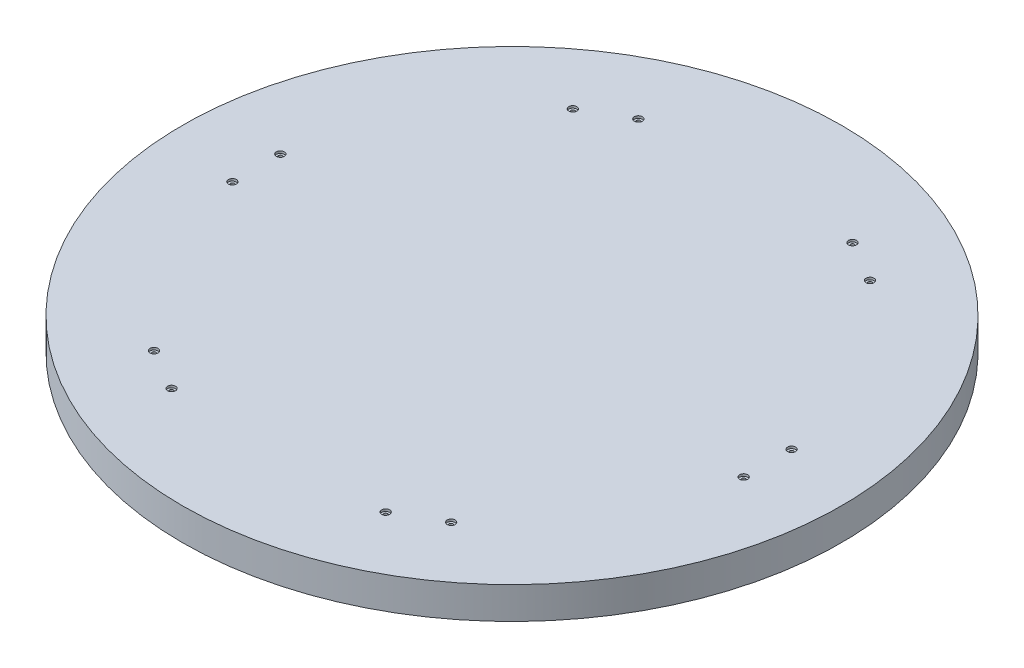
SolidWorks part; units mm, degrees
ref_plane "Front Plane" through (0, 0, 0) normal (0, 0, 1) x (1, 0, 0)
ref_plane "Top Plane" through (0, 0, 0) normal (0, 1, 0) x (1, 0, 0)
ref_plane "Right Plane" through (0, 0, 0) normal (1, 0, 0) x (0, 0, -1)
sketch "Sketch1" plane through (0, 0, 0) normal (0, 1, 0) x (1, 0, 0)
  circle A0 centre (0, 0) radius 261.9375
extrude "Boss-Extrude1" add sketch "Sketch1" along normal blind 25.4
sketch "Sketch6" plane through (0, 0, 0) normal (0, -1, 0) x (1, 0, 0)
  line L0 (203.2, 19.05) -> (203.2, -19.05) construction
  line L1 (215.9, 19.05) -> (215.9, -19.05)
  line L2 (190.5, 19.05) -> (190.5, -19.05)
  line L3 (203.2, -16.5451) -> (201.0307, -17.7976) construction
  line L4 (201.0307, -17.7976) -> (201.0307, -20.3024) construction
  line L5 (201.0307, -20.3024) -> (203.2, -21.5549) construction
  line L6 (203.2, -21.5549) -> (205.3693, -20.3024) construction
  line L7 (205.3693, -20.3024) -> (205.3693, -17.7976) construction
  line L8 (205.3693, -17.7976) -> (203.2, -16.5451) construction
  line L9 (203.2, 22.1294) -> (201.0307, 20.8769) construction
  line L10 (201.0307, 20.8769) -> (201.0307, 18.372) construction
  line L11 (201.0307, 18.372) -> (203.2, 17.1196) construction
  line L12 (203.2, 17.1196) -> (205.3693, 18.372) construction
  line L13 (205.3693, 18.372) -> (205.3693, 20.8769) construction
  line L14 (205.3693, 20.8769) -> (203.2, 22.1294) construction
  line L15 (0, 0) -> (203.2, 0) construction
  line L16 (87.2715, -184.2489) -> (85.1022, -182.9965) construction
  line L17 (85.1022, -182.9965) -> (82.9329, -184.2489) construction
  line L18 (82.9329, -184.2489) -> (82.9329, -186.7538) construction
  line L19 (82.9329, -186.7538) -> (85.1022, -188.0063) construction
  line L20 (85.1022, -188.0063) -> (87.2715, -186.7538) construction
  line L21 (87.2715, -186.7538) -> (87.2715, -184.2489) construction
  line L22 (120.7646, -164.9117) -> (118.5953, -163.6592) construction
  line L23 (118.5953, -163.6592) -> (116.426, -164.9117) construction
  line L24 (116.426, -164.9117) -> (116.426, -167.4166) construction
  line L25 (116.426, -167.4166) -> (118.5953, -168.669) construction
  line L26 (118.5953, -168.669) -> (120.7646, -167.4166) construction
  line L27 (120.7646, -167.4166) -> (120.7646, -164.9117) construction
  line L28 (0, 0) -> (101.6, -175.9764) construction
  line L29 (118.0978, -166.4514) -> (85.1022, -185.5014) construction
  line L30 (124.4478, -177.4499) -> (91.4522, -196.4999)
  line L31 (111.7478, -155.4528) -> (78.7522, -174.5028)
  line L32 (-115.9285, -167.7038) -> (-115.9285, -165.1989) construction
  line L33 (-115.9285, -165.1989) -> (-118.0978, -163.9465) construction
  line L34 (-118.0978, -163.9465) -> (-120.2671, -165.1989) construction
  line L35 (-120.2671, -165.1989) -> (-120.2671, -167.7038) construction
  line L36 (-120.2671, -167.7038) -> (-118.0978, -168.9563) construction
  line L37 (-118.0978, -168.9563) -> (-115.9285, -167.7038) construction
  line L38 (-82.4354, -187.0411) -> (-82.4354, -184.5362) construction
  line L39 (-82.4354, -184.5362) -> (-84.6047, -183.2837) construction
  line L40 (-84.6047, -183.2837) -> (-86.774, -184.5362) construction
  line L41 (-86.774, -184.5362) -> (-86.774, -187.0411) construction
  line L42 (-86.774, -187.0411) -> (-84.6047, -188.2935) construction
  line L43 (-84.6047, -188.2935) -> (-82.4354, -187.0411) construction
  line L44 (0, 0) -> (-101.6, -175.9764) construction
  line L45 (-85.1022, -185.5014) -> (-118.0978, -166.4514) construction
  line L46 (-91.4522, -196.4999) -> (-124.4478, -177.4499)
  line L47 (-78.7522, -174.5028) -> (-111.7478, -155.4528)
  line L48 (-203.2, 16.5451) -> (-201.0307, 17.7976) construction
  line L49 (-201.0307, 17.7976) -> (-201.0307, 20.3024) construction
  line L50 (-201.0307, 20.3024) -> (-203.2, 21.5549) construction
  line L51 (-203.2, 21.5549) -> (-205.3693, 20.3024) construction
  line L52 (-205.3693, 20.3024) -> (-205.3693, 17.7976) construction
  line L53 (-205.3693, 17.7976) -> (-203.2, 16.5451) construction
  line L54 (-203.2, -22.1294) -> (-201.0307, -20.8769) construction
  line L55 (-201.0307, -20.8769) -> (-201.0307, -18.372) construction
  line L56 (-201.0307, -18.372) -> (-203.2, -17.1196) construction
  line L57 (-203.2, -17.1196) -> (-205.3693, -18.372) construction
  line L58 (-205.3693, -18.372) -> (-205.3693, -20.8769) construction
  line L59 (-205.3693, -20.8769) -> (-203.2, -22.1294) construction
  line L60 (0, 0) -> (-203.2, 0) construction
  line L61 (-203.2, -19.05) -> (-203.2, 19.05) construction
  line L62 (-215.9, -19.05) -> (-215.9, 19.05)
  line L63 (-190.5, -19.05) -> (-190.5, 19.05)
  line L64 (-87.2715, 184.2489) -> (-85.1022, 182.9965) construction
  line L65 (-85.1022, 182.9965) -> (-82.9329, 184.2489) construction
  line L66 (-82.9329, 184.2489) -> (-82.9329, 186.7538) construction
  line L67 (-82.9329, 186.7538) -> (-85.1022, 188.0063) construction
  line L68 (-85.1022, 188.0063) -> (-87.2715, 186.7538) construction
  line L69 (-87.2715, 186.7538) -> (-87.2715, 184.2489) construction
  line L70 (-120.7646, 164.9117) -> (-118.5953, 163.6592) construction
  line L71 (-118.5953, 163.6592) -> (-116.426, 164.9117) construction
  line L72 (-116.426, 164.9117) -> (-116.426, 167.4166) construction
  line L73 (-116.426, 167.4166) -> (-118.5953, 168.669) construction
  line L74 (-118.5953, 168.669) -> (-120.7646, 167.4166) construction
  line L75 (-120.7646, 167.4166) -> (-120.7646, 164.9117) construction
  line L76 (0, 0) -> (-101.6, 175.9764) construction
  line L77 (-118.0978, 166.4514) -> (-85.1022, 185.5014) construction
  line L78 (-124.4478, 177.4499) -> (-91.4522, 196.4999)
  line L79 (-111.7478, 155.4528) -> (-78.7522, 174.5028)
  line L80 (115.9285, 167.7038) -> (115.9285, 165.1989) construction
  line L81 (115.9285, 165.1989) -> (118.0978, 163.9465) construction
  line L82 (118.0978, 163.9465) -> (120.2671, 165.1989) construction
  line L83 (120.2671, 165.1989) -> (120.2671, 167.7038) construction
  line L84 (120.2671, 167.7038) -> (118.0978, 168.9563) construction
  line L85 (118.0978, 168.9563) -> (115.9285, 167.7038) construction
  line L86 (82.4354, 187.0411) -> (82.4354, 184.5362) construction
  line L87 (82.4354, 184.5362) -> (84.6047, 183.2837) construction
  line L88 (84.6047, 183.2837) -> (86.774, 184.5362) construction
  line L89 (86.774, 184.5362) -> (86.774, 187.0411) construction
  line L90 (86.774, 187.0411) -> (84.6047, 188.2935) construction
  line L91 (84.6047, 188.2935) -> (82.4354, 187.0411) construction
  line L92 (0, 0) -> (101.6, 175.9764) construction
  line L93 (85.1022, 185.5014) -> (118.0978, 166.4514) construction
  line L94 (91.4522, 196.4999) -> (124.4478, 177.4499)
  line L95 (78.7522, 174.5028) -> (111.7478, 155.4528)
  arc A0 (215.9, 19.05) -> (190.5, 19.05) centre (203.2, 19.05) ccw
  arc A1 (190.5, -19.05) -> (215.9, -19.05) centre (203.2, -19.05) ccw
  circle A2 centre (203.2, -19.05) radius 2.1693 construction
  circle A3 centre (203.2, 19.6245) radius 2.1693 construction
  circle A4 centre (203.2, -19.05) radius 1.524 construction
  circle A5 centre (203.2, 19.6245) radius 1.524 construction
  circle A6 centre (85.1022, -185.5014) radius 2.1693 construction
  circle A7 centre (118.5953, -166.1641) radius 2.1693 construction
  circle A8 centre (85.1022, -185.5014) radius 1.524 construction
  circle A9 centre (118.5953, -166.1641) radius 1.524 construction
  arc A10 (124.4478, -177.4499) -> (111.7478, -155.4528) centre (118.0978, -166.4514) ccw
  arc A11 (78.7522, -174.5028) -> (91.4522, -196.4999) centre (85.1022, -185.5014) ccw
  circle A12 centre (-118.0978, -166.4514) radius 2.1693 construction
  circle A13 centre (-84.6047, -185.7886) radius 2.1693 construction
  circle A14 centre (-118.0978, -166.4514) radius 1.524 construction
  circle A15 centre (-84.6047, -185.7886) radius 1.524 construction
  arc A16 (-91.4522, -196.4999) -> (-78.7522, -174.5028) centre (-85.1022, -185.5014) ccw
  arc A17 (-111.7478, -155.4528) -> (-124.4478, -177.4499) centre (-118.0978, -166.4514) ccw
  circle A18 centre (-203.2, 19.05) radius 2.1693 construction
  circle A19 centre (-203.2, -19.6245) radius 2.1693 construction
  circle A20 centre (-203.2, 19.05) radius 1.524 construction
  circle A21 centre (-203.2, -19.6245) radius 1.524 construction
  arc A22 (-215.9, -19.05) -> (-190.5, -19.05) centre (-203.2, -19.05) ccw
  arc A23 (-190.5, 19.05) -> (-215.9, 19.05) centre (-203.2, 19.05) ccw
  circle A24 centre (-85.1022, 185.5014) radius 2.1693 construction
  circle A25 centre (-118.5953, 166.1641) radius 2.1693 construction
  circle A26 centre (-85.1022, 185.5014) radius 1.524 construction
  circle A27 centre (-118.5953, 166.1641) radius 1.524 construction
  arc A28 (-124.4478, 177.4499) -> (-111.7478, 155.4528) centre (-118.0978, 166.4514) ccw
  arc A29 (-78.7522, 174.5028) -> (-91.4522, 196.4999) centre (-85.1022, 185.5014) ccw
  circle A30 centre (118.0978, 166.4514) radius 2.1693 construction
  circle A31 centre (84.6047, 185.7886) radius 2.1693 construction
  circle A32 centre (118.0978, 166.4514) radius 1.524 construction
  circle A33 centre (84.6047, 185.7886) radius 1.524 construction
  arc A34 (91.4522, 196.4999) -> (78.7522, 174.5028) centre (85.1022, 185.5014) ccw
  arc A35 (111.7478, 155.4528) -> (124.4478, 177.4499) centre (118.0978, 166.4514) ccw
  point P2 (203.2, 0)
  point P32 (101.6, -175.9764)
  point P58 (-101.6, -175.9764)
  point P84 (-203.2, 0)
  point P110 (-101.6, 175.9764)
  point P136 (101.6, 175.9764)
  point P160 (0, 0)
extrude "Cut-Extrude4" cut sketch "Sketch6" against normal blind 12.7
sketch "Sketch7" plane through (0, 12.7, 0) normal (0, -1, 0) x (1, 0, 0)
  line L0 (203.2, 19.05) -> (203.2, -19.05) construction
  line L1 (215.9, 19.05) -> (215.9, -19.05) construction
  line L2 (190.5, 19.05) -> (190.5, -19.05) construction
  line L3 (203.2, -16.5451) -> (201.0307, -17.7975) construction
  line L4 (201.0307, -17.7975) -> (201.0307, -20.3024) construction
  line L5 (201.0307, -20.3024) -> (203.2, -21.5549) construction
  line L6 (203.2, -21.5549) -> (205.3693, -20.3024) construction
  line L7 (205.3693, -20.3024) -> (205.3693, -17.7975) construction
  line L8 (205.3693, -17.7975) -> (203.2, -16.5451) construction
  line L9 (203.2, 21.5549) -> (201.0307, 20.3025) construction
  line L10 (201.0307, 20.3025) -> (201.0307, 17.7976) construction
  line L11 (201.0307, 17.7976) -> (203.2, 16.5451) construction
  line L12 (203.2, 16.5451) -> (205.3693, 17.7976) construction
  line L13 (205.3693, 17.7976) -> (205.3693, 20.3025) construction
  line L14 (205.3693, 20.3025) -> (203.2, 21.5549) construction
  line L15 (190.5, -19.05) -> (203.2, -19.05) construction
  line L16 (87.2715, -184.2489) -> (85.1022, -182.9965) construction
  line L17 (85.1022, -182.9965) -> (82.9329, -184.2489) construction
  line L18 (82.9329, -184.2489) -> (82.9329, -186.7538) construction
  line L19 (82.9329, -186.7538) -> (85.1022, -188.0062) construction
  line L20 (85.1022, -188.0062) -> (87.2715, -186.7538) construction
  line L21 (87.2715, -186.7538) -> (87.2715, -184.2489) construction
  line L22 (120.2671, -165.1989) -> (118.0978, -163.9465) construction
  line L23 (118.0978, -163.9465) -> (115.9285, -165.1989) construction
  line L24 (115.9285, -165.1989) -> (115.9285, -167.7038) construction
  line L25 (115.9285, -167.7038) -> (118.0978, -168.9562) construction
  line L26 (118.0978, -168.9562) -> (120.2671, -167.7038) construction
  line L27 (120.2671, -167.7038) -> (120.2671, -165.1989) construction
  line L28 (78.7522, -174.5028) -> (85.1022, -185.5014) construction
  line L29 (118.0978, -166.4514) -> (85.1022, -185.5014) construction
  line L30 (124.4478, -177.4499) -> (91.4522, -196.4999) construction
  line L31 (111.7478, -155.4528) -> (78.7522, -174.5028) construction
  line L32 (-115.9285, -167.7038) -> (-115.9285, -165.1989) construction
  line L33 (-115.9285, -165.1989) -> (-118.0978, -163.9465) construction
  line L34 (-118.0978, -163.9465) -> (-120.2671, -165.1989) construction
  line L35 (-120.2671, -165.1989) -> (-120.2671, -167.7038) construction
  line L36 (-120.2671, -167.7038) -> (-118.0978, -168.9563) construction
  line L37 (-118.0978, -168.9563) -> (-115.9285, -167.7038) construction
  line L38 (-82.9329, -186.7538) -> (-82.9329, -184.2489) construction
  line L39 (-82.9329, -184.2489) -> (-85.1022, -182.9965) construction
  line L40 (-85.1022, -182.9965) -> (-87.2715, -184.2489) construction
  line L41 (-87.2715, -184.2489) -> (-87.2715, -186.7538) construction
  line L42 (-87.2715, -186.7538) -> (-85.1022, -188.0063) construction
  line L43 (-85.1022, -188.0063) -> (-82.9329, -186.7538) construction
  line L44 (-111.7478, -155.4528) -> (-118.0978, -166.4514) construction
  line L45 (-85.1022, -185.5014) -> (-118.0978, -166.4514) construction
  line L46 (-91.4522, -196.4999) -> (-124.4478, -177.4499) construction
  line L47 (-78.7522, -174.5028) -> (-111.7478, -155.4528) construction
  line L48 (-203.2, 16.5451) -> (-201.0307, 17.7975) construction
  line L49 (-201.0307, 17.7975) -> (-201.0307, 20.3024) construction
  line L50 (-201.0307, 20.3024) -> (-203.2, 21.5549) construction
  line L51 (-203.2, 21.5549) -> (-205.3693, 20.3024) construction
  line L52 (-205.3693, 20.3024) -> (-205.3693, 17.7975) construction
  line L53 (-205.3693, 17.7975) -> (-203.2, 16.5451) construction
  line L54 (-203.2, -21.5549) -> (-201.0307, -20.3025) construction
  line L55 (-201.0307, -20.3025) -> (-201.0307, -17.7976) construction
  line L56 (-201.0307, -17.7976) -> (-203.2, -16.5451) construction
  line L57 (-203.2, -16.5451) -> (-205.3693, -17.7976) construction
  line L58 (-205.3693, -17.7976) -> (-205.3693, -20.3025) construction
  line L59 (-205.3693, -20.3025) -> (-203.2, -21.5549) construction
  line L60 (-190.5, 19.05) -> (-203.2, 19.05) construction
  line L61 (-203.2, -19.05) -> (-203.2, 19.05) construction
  line L62 (-215.9, -19.05) -> (-215.9, 19.05) construction
  line L63 (-190.5, -19.05) -> (-190.5, 19.05) construction
  line L64 (-87.2715, 184.2489) -> (-85.1022, 182.9965) construction
  line L65 (-85.1022, 182.9965) -> (-82.9329, 184.2489) construction
  line L66 (-82.9329, 184.2489) -> (-82.9329, 186.7538) construction
  line L67 (-82.9329, 186.7538) -> (-85.1022, 188.0062) construction
  line L68 (-85.1022, 188.0062) -> (-87.2715, 186.7538) construction
  line L69 (-87.2715, 186.7538) -> (-87.2715, 184.2489) construction
  line L70 (-120.2671, 165.1989) -> (-118.0978, 163.9465) construction
  line L71 (-118.0978, 163.9465) -> (-115.9285, 165.1989) construction
  line L72 (-115.9285, 165.1989) -> (-115.9285, 167.7038) construction
  line L73 (-115.9285, 167.7038) -> (-118.0978, 168.9562) construction
  line L74 (-118.0978, 168.9562) -> (-120.2671, 167.7038) construction
  line L75 (-120.2671, 167.7038) -> (-120.2671, 165.1989) construction
  line L76 (-78.7522, 174.5028) -> (-85.1022, 185.5014) construction
  line L77 (-118.0978, 166.4514) -> (-85.1022, 185.5014) construction
  line L78 (-124.4478, 177.4499) -> (-91.4522, 196.4999) construction
  line L79 (-111.7478, 155.4528) -> (-78.7522, 174.5028) construction
  line L80 (115.9285, 167.7038) -> (115.9285, 165.1989) construction
  line L81 (115.9285, 165.1989) -> (118.0978, 163.9465) construction
  line L82 (118.0978, 163.9465) -> (120.2671, 165.1989) construction
  line L83 (120.2671, 165.1989) -> (120.2671, 167.7038) construction
  line L84 (120.2671, 167.7038) -> (118.0978, 168.9563) construction
  line L85 (118.0978, 168.9563) -> (115.9285, 167.7038) construction
  line L86 (82.9329, 186.7538) -> (82.9329, 184.2489) construction
  line L87 (82.9329, 184.2489) -> (85.1022, 182.9965) construction
  line L88 (85.1022, 182.9965) -> (87.2715, 184.2489) construction
  line L89 (87.2715, 184.2489) -> (87.2715, 186.7538) construction
  line L90 (87.2715, 186.7538) -> (85.1022, 188.0063) construction
  line L91 (85.1022, 188.0063) -> (82.9329, 186.7538) construction
  line L92 (111.7478, 155.4528) -> (118.0978, 166.4514) construction
  line L93 (85.1022, 185.5014) -> (118.0978, 166.4514) construction
  line L94 (91.4522, 196.4999) -> (124.4478, 177.4499) construction
  line L95 (78.7522, 174.5028) -> (111.7478, 155.4528) construction
  line L97 (0, 0) -> (-101.6, 175.9764) construction
  arc A0 (215.9, 19.05) -> (190.5, 19.05) centre (203.2, 19.05) ccw construction
  arc A1 (190.5, -19.05) -> (215.9, -19.05) centre (203.2, -19.05) ccw construction
  circle A2 centre (203.2, -19.05) radius 2.1693 construction
  circle A3 centre (203.2, 19.05) radius 2.1693 construction
  circle A4 centre (203.2, -19.05) radius 1.524
  circle A5 centre (203.2, 19.05) radius 1.524
  circle A6 centre (85.1022, -185.5014) radius 1.524
  circle A7 centre (118.0978, -166.4514) radius 1.524
  circle A8 centre (85.1022, -185.5014) radius 2.1693 construction
  circle A9 centre (118.0978, -166.4514) radius 2.1693 construction
  arc A10 (124.4478, -177.4499) -> (111.7478, -155.4528) centre (118.0978, -166.4514) ccw construction
  arc A11 (78.7522, -174.5028) -> (91.4522, -196.4999) centre (85.1022, -185.5014) ccw construction
  circle A12 centre (-118.0978, -166.4514) radius 1.524
  circle A13 centre (-85.1022, -185.5014) radius 1.524
  circle A14 centre (-118.0978, -166.4514) radius 2.1693 construction
  circle A15 centre (-85.1022, -185.5014) radius 2.1693 construction
  arc A16 (-91.4522, -196.4999) -> (-78.7522, -174.5028) centre (-85.1022, -185.5014) ccw construction
  arc A17 (-111.7478, -155.4528) -> (-124.4478, -177.4499) centre (-118.0978, -166.4514) ccw construction
  circle A18 centre (-203.2, 19.05) radius 1.524
  circle A19 centre (-203.2, -19.05) radius 1.524
  circle A20 centre (-203.2, 19.05) radius 2.1693 construction
  circle A21 centre (-203.2, -19.05) radius 2.1693 construction
  arc A22 (-215.9, -19.05) -> (-190.5, -19.05) centre (-203.2, -19.05) ccw construction
  arc A23 (-190.5, 19.05) -> (-215.9, 19.05) centre (-203.2, 19.05) ccw construction
  circle A24 centre (-85.1022, 185.5014) radius 1.524
  circle A25 centre (-118.0978, 166.4514) radius 1.524
  circle A26 centre (-85.1022, 185.5014) radius 2.1693 construction
  circle A27 centre (-118.0978, 166.4514) radius 2.1693 construction
  arc A28 (-124.4478, 177.4499) -> (-111.7478, 155.4528) centre (-118.0978, 166.4514) ccw construction
  arc A29 (-78.7522, 174.5028) -> (-91.4522, 196.4999) centre (-85.1022, 185.5014) ccw construction
  circle A30 centre (118.0978, 166.4514) radius 1.524
  circle A31 centre (85.1022, 185.5014) radius 1.524
  circle A32 centre (118.0978, 166.4514) radius 2.1693 construction
  circle A33 centre (85.1022, 185.5014) radius 2.1693 construction
  arc A34 (91.4522, 196.4999) -> (78.7522, 174.5028) centre (85.1022, 185.5014) ccw construction
  arc A35 (111.7478, 155.4528) -> (124.4478, 177.4499) centre (118.0978, 166.4514) ccw construction
  point P2 (203.2, 0)
  point P33 (101.6, -175.9764)
  point P60 (-101.6, -175.9764)
  point P87 (-203.2, 0)
  point P114 (-101.6, 175.9764)
  point P141 (101.6, 175.9764)
  point P166 (0, 0)
  dimension "D1" = 6
extrude "Cut-Extrude5" cut sketch "Sketch7" against normal through all
sketch "Sketch8" plane through (0, 25.4, 0) normal (0, 1, 0) x (1, 0, 0)
  line L1 (-101.7546, -175.8871) -> (0, 0) construction
  line L2 (-118.0978, -167.9754) -> (-118.0978, -164.9274) construction
  line L3 (-203.2, 0.1785) -> (0, 0) construction
  line L4 (-204.5198, 18.288) -> (-201.8802, 19.812) construction
  line L5 (-201.8802, -18.288) -> (-204.5198, -19.812) construction
  line L6 (-203.2, 19.05) -> (-203.2, -19.05) construction
  line L8 (-101.4454, 176.0656) -> (0, 0) construction
  line L9 (-86.422, 186.2634) -> (-83.7824, 184.7394) construction
  line L10 (-116.778, 165.6894) -> (-119.4176, 167.2134) construction
  line L11 (-85.1022, 185.5014) -> (-118.0978, 166.4514) construction
  line L12 (-85.1022, -183.9774) -> (-85.1022, -187.0254) construction
  line L14 (-118.0978, -166.4514) -> (-85.1022, -185.5014) construction
  line L16 (101.7546, 175.8871) -> (0, 0) construction
  line L17 (118.0978, 167.9754) -> (118.0978, 164.9274) construction
  line L18 (85.1022, 183.9774) -> (85.1022, 187.0254) construction
  line L19 (118.0978, 166.4514) -> (85.1022, 185.5014) construction
  line L21 (203.2, -0.1785) -> (0, 0) construction
  line L22 (204.5198, -18.288) -> (201.8802, -19.812) construction
  line L23 (201.8802, 18.288) -> (204.5198, 19.812) construction
  line L24 (203.2, -19.05) -> (203.2, 19.05) construction
  line L26 (101.4454, -176.0656) -> (0, 0) construction
  line L27 (86.422, -186.2634) -> (83.7824, -184.7394) construction
  line L28 (116.778, -165.6894) -> (119.4176, -167.2134) construction
  line L29 (85.1022, -185.5014) -> (118.0978, -166.4514) construction
  circle A0 centre (-203.2, -19.05) radius 3.175
  circle A1 centre (-203.2, 19.05) radius 3.175
  circle A2 centre (-118.0978, 166.4514) radius 3.175
  circle A3 centre (-85.1022, 185.5014) radius 3.175
  circle A4 centre (-85.1022, -185.5014) radius 3.175
  circle A5 centre (-118.0978, -166.4514) radius 3.175
  circle A6 centre (85.1022, 185.5014) radius 3.175
  circle A7 centre (118.0978, 166.4514) radius 3.175
  circle A8 centre (203.2, 19.05) radius 3.175
  circle A9 centre (203.2, -19.05) radius 3.175
  circle A10 centre (118.0978, -166.4514) radius 3.175
  circle A11 centre (85.1022, -185.5014) radius 3.175
  circle A12 centre (-85.1022, -185.5014) radius 1.524 construction
  circle A13 centre (-118.0978, -166.4514) radius 1.524 construction
  point P4 (0.0192, 0.0001)
  point P5 (0.0095, 0.0167)
  point P71 (0, 0)
  dimension "D1" = 6
extrude "Cut-Extrude6" cut sketch "Sketch8" against normal blind 1.778
sketch "Sketch9" plane through (0, 0, 0) normal (0, -1, 0) x (1, 0, 0)
  circle A0 centre (0, 0) radius 25.4
extrude "Boss-Extrude2" add sketch "Sketch9" along normal blind 10.16
sketch "Sketch10" plane through (0, -10.16, 0) normal (0, -1, 0) x (1, 0, 0)
  line L0 (0, -2.032) -> (0, 1.524) construction
  line L1 (-1.344, 1.524) -> (1.344, 1.524)
  arc A0 (-1.344, 1.524) -> (1.344, 1.524) centre (0, 0) ccw
extrude "Cut-Extrude7" cut sketch "Sketch10" against normal blind 19.05
sketch "Sketch12" plane through (0, 0, 0) normal (0, -1, 0) x (1, 0, 0)
  line L0 (0, 0) -> (-11.1642, -177.4492) construction
  line L1 (0, 0) -> (0, -177.8) construction
  line L2 (0, 0) -> (-5.5848, -177.7123) construction
  line L3 (0, 0) -> (11.1642, -177.4492) construction
  line L4 (0, 0) -> (5.5848, -177.7123) construction
  line L5 (-5.5848, -177.7123) -> (-5.5848, -176.764) construction
  line L6 (0, 0) -> (-8.0783, -177.6164) construction
  circle A0 centre (0, 0) radius 177.8
  ellipse E0 centre (-0.0001, -265.6631) end of major axis (-0.0001, -164.0631) minor radius 11.1642
